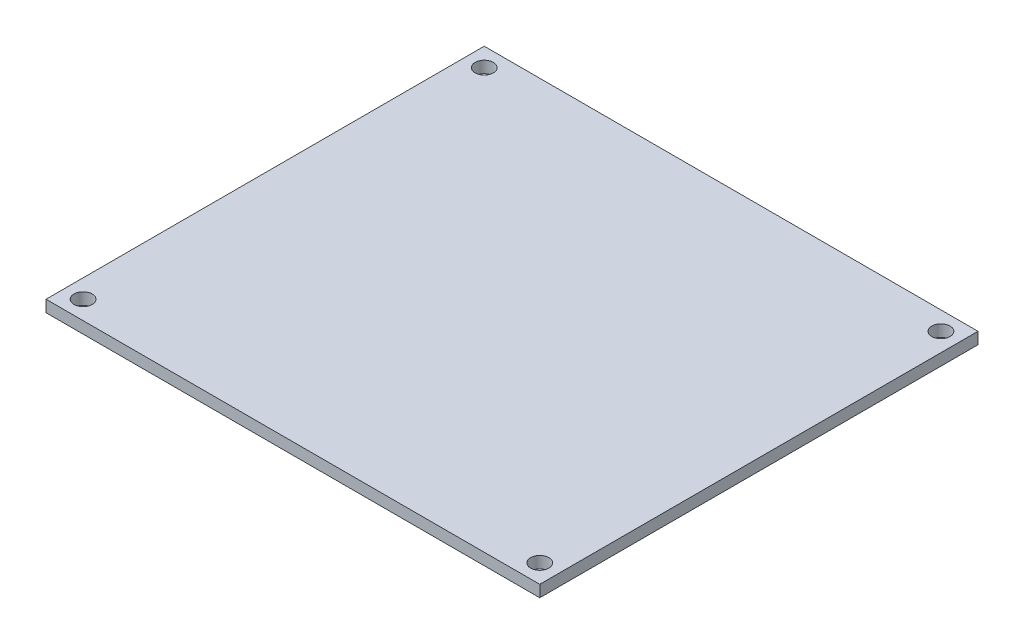
SolidWorks part; units mm, degrees
ref_plane "Front Plane" through (0, 0, 0) normal (0, 0, 1) x (1, 0, 0)
ref_plane "Top Plane" through (0, 0, 0) normal (0, 1, 0) x (1, 0, 0)
ref_plane "Right Plane" through (0, 0, 0) normal (1, 0, 0) x (0, 0, -1)
sketch "Sketch1" plane through (0, 0, 0) normal (0, 1, 0) x (1, 0, 0)
  line L0 (-31.26, 27.46) -> (31.26, 27.46) construction
  line L1 (-33.8, -30) -> (33.8, -30)
  line L2 (-33.8, -30) -> (-33.8, 30)
  line L3 (-33.8, 30) -> (33.8, 30)
  line L4 (33.8, -30) -> (33.8, 30)
  line L5 (-33.8, -30) -> (33.8, 30) construction
  line L6 (-33.8, 30) -> (33.8, -30) construction
  line L7 (31.26, -27.46) -> (31.26, 27.46) construction
  line L8 (-31.26, -27.46) -> (31.26, -27.46) construction
  line L9 (-31.26, -27.46) -> (-31.26, 27.46) construction
  point P0 (0, 0)
  dimension "D1" = 60
  dimension "D2" = 67.6
  dimension "D3" = 2.54
extrude "Boss-Extrude1" add sketch "Sketch1" along normal blind 1.6
sketch "Sketch2" plane through (0, 1.6, 0) normal (0, 1, 0) x (1, 0, 0)
  point P0 (-31.26, 27.46)
  point P3 (31.26, 27.46)
  point P6 (31.26, -27.46)
  point P9 (-31.26, -27.46)
hole_wizard "Ø2.5mm Dowel Hole1" positions "Sketch2" profile "Sketch3" hole size "Ø2.5" standard "ANSI Metric" end condition through all
sketch "Sketch3" plane through (-31.26, 1.6, -27.46) normal (1, 0, 0) x (0, 0, 1)
  line L0 (0, 0) -> (0, 1.6)
  line L1 (0, 1.6) -> (1.25, 1.6)
  line L2 (1.25, 1.6) -> (1.25, 0)
  line L5 (1.25, 0) -> (0, 0)
  line L11 (0, -6.35) -> (0, 107.95) construction
  dimension "Thru Hole Dia." = 2.5
  dimension "Thru Hole Depth" = 1.6
